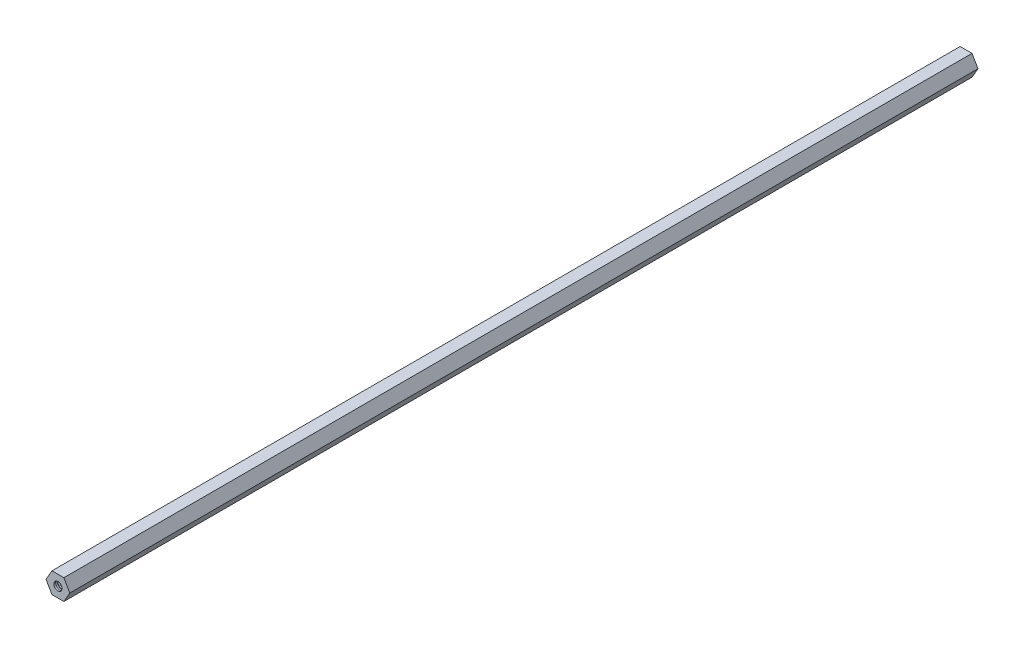
SolidWorks part; units mm, degrees
material "7075-T6 (SN)"
ref_plane "Alzado" through (0, 0, 0) normal (0, 0, 1) x (1, 0, 0)
ref_plane "Planta" through (0, 0, 0) normal (0, 1, 0) x (1, 0, 0)
ref_plane "Vista lateral" through (0, 0, 0) normal (1, 0, 0) x (0, 0, -1)
sketch "Croquis2" plane through (0, 0, 0) normal (0, 0, 1) x (1, 0, 0)
  line L1 (3.6662, -6.35) -> (7.3323, 0)
  line L2 (7.3323, 0) -> (3.6662, 6.35)
  line L3 (3.6662, 6.35) -> (-3.6662, 6.35)
  line L4 (-3.6662, 6.35) -> (-7.3323, 0)
  line L5 (-7.3323, 0) -> (-3.6662, -6.35)
  line L6 (-3.6662, -6.35) -> (3.6662, -6.35)
  circle A0 centre (0, 0) radius 6.35 construction
  dimension "D1" = 12.7
extrude "Extrusión Hex Profile" add sketch "Croquis2" along normal mid plane 558.8
sketch "Croquis3" plane through (0, 0, 0) normal (0, 0, 1) x (1, 0, 0)
  circle A0 centre (0, 0) radius 2.5527
  dimension "D1" = 5.1054
extrude "Tap Hole 1" cut sketch "Croquis3" against normal blind 19.05 from surface starting at face at (0, 0, 279.4)
extrude "Tap Hole 2" cut sketch "Croquis3<3>" along normal blind 19.05 from surface starting at face at (0, 0, -279.4)
sketch "Croquis3<3>" plane through (0, 0, 0) normal (0, 0, 1) x (1, 0, 0) same geometry as "Croquis3"
sketch "Croquis7" plane through (0, 0, 0) normal (0, 0, 1) x (1, 0, 0)
  circle A0 centre (0, 0) radius 6.8707
  dimension "D1" = 13.7414
extrude "ThunderHex" [suppressed] cut sketch "Croquis7" against normal through all both and the other way through all flip side to cut
sketch "Croquis8" plane through (0, 0, 0) normal (0, 1, 0) x (1, 0, 0)
  line L0 (0, -279.4) -> (-5.5563, -279.4) construction
  line L1 (3.6662, -279.4) -> (-3.6662, -279.4) construction
  line L3 (0, -279.4) -> (0, 0) construction
  line L4 (-5.5563, -279.4) -> (-6.35, -278.6062)
  line L5 (-6.35, -278.6062) -> (-6.35, -277.8125)
  line L6 (-6.35, -277.8125) -> (-5.9055, -277.8125)
  line L7 (-5.9055, -277.8125) -> (-5.9055, -276.225)
  line L8 (-5.9055, -276.225) -> (-12.7, -276.225)
  line L9 (-12.7, -276.225) -> (-12.7, -279.4)
  line L10 (-12.7, -279.4) -> (-5.5563, -279.4)
  line L11 (-3.6662, -279.4) -> (-7.3323, -279.4) construction
  dimension "D1" = 11.811
  dimension "D2" = 12.7
  dimension "D3" = 45
  dimension "D4" = 0.7937
  dimension "D6" = 0.7937
  dimension "D7" = 3.175
  dimension "D8" = 25.4
revolve "Retaining Ring 1" [suppressed] cut sketch "Croquis8" angle 360 about L3
sketch "Croquis9" plane through (0, 0, 0) normal (0, -1, 0) x (1, 0, 0)
  line L0 (0, -279.4) -> (-5.5563, -279.4) construction
  line L3 (0, -279.4) -> (0, 0) construction
  line L4 (-5.5563, -279.4) -> (-6.35, -278.6062)
  line L5 (-6.35, -278.6062) -> (-6.35, -277.8125)
  line L6 (-6.35, -277.8125) -> (-5.9055, -277.8125)
  line L7 (-5.9055, -277.8125) -> (-5.9055, -276.225)
  line L8 (-5.9055, -276.225) -> (-12.7, -276.225)
  line L9 (-12.7, -276.225) -> (-12.7, -279.4)
  line L10 (-12.7, -279.4) -> (-5.5563, -279.4)
  line L12 (-3.6662, -279.4) -> (3.6662, -279.4) construction
  line L13 (-7.3323, -279.4) -> (-3.6662, -279.4) construction
  dimension "D1" = 11.811
  dimension "D2" = 12.7
  dimension "D3" = 45
  dimension "D4" = 0.7937
  dimension "D6" = 0.7937
  dimension "D7" = 3.175
  dimension "D8" = 25.4
revolve "Retaining Ring 2" [suppressed] cut sketch "Croquis9" angle 360 about L3
sketch "Croquis10" plane through (0, 0, 0) normal (0, 1, 0) x (1, 0, 0)
  line L0 (0, -279.4) -> (0, 0) construction
  line L1 (3.6662, -279.4) -> (-3.6662, -279.4) construction
  line L2 (0, -279.4) -> (-5.5563, -279.4) construction
  line L3 (-3.6662, -279.4) -> (-7.3323, -279.4) construction
  line L4 (-5.5563, -279.4) -> (-6.35, -278.6062)
  line L5 (-6.35, -278.6062) -> (-6.35, -271.4498)
  line L6 (-6.35, -271.4498) -> (-9.525, -271.4498)
  line L7 (-9.525, -271.4498) -> (-9.525, -279.4)
  line L8 (-9.525, -279.4) -> (-5.5563, -279.4)
  dimension "D2" = 12.7
  dimension "D1" = 45
  dimension "D3" = 0.7937
  dimension "D4" = 7.9502
  dimension "D5" = 19.05
revolve "Round End 1" [suppressed] cut sketch "Croquis10" angle 360 about L0
sketch "Croquis12" plane through (0, 0, 0) normal (0, -1, 0) x (1, 0, 0)
  line L0 (0, -279.4) -> (0, 0) construction
  line L2 (0, -279.4) -> (-5.5563, -279.4) construction
  line L4 (-5.5563, -279.4) -> (-6.35, -278.6062)
  line L5 (-6.35, -278.6062) -> (-6.35, -271.4498)
  line L6 (-6.35, -271.4498) -> (-9.525, -271.4498)
  line L7 (-9.525, -271.4498) -> (-9.525, -279.4)
  line L8 (-9.525, -279.4) -> (-5.5563, -279.4)
  line L9 (-3.6662, -279.4) -> (3.6662, -279.4) construction
  dimension "D1" = 45
  dimension "D3" = 0.7937
  dimension "D4" = 7.9502
  dimension "D2" = 12.7
  dimension "D5" = 19.05
revolve "Round End 2" [suppressed] cut sketch "Croquis12" angle 360 about L0
thread "Rosca1" pitch 1.27 method cut profile "Perfil de rosca1" start angle 0, offset 0, length 0, pitch 1.27, diameter 5.1054
ref_plane "Plano1" through (2.5527, 0, -279.4) normal (0, -1, 0) x (1, 0, 0)
sketch "Perfil de rosca1" plane through (2.5527, 0, -279.4) normal (0, -1, 0) x (1, 0, 0)
  line L0 (0, 0) -> (0, 1.27) construction
  line L1 (0, 0) -> (0.6874, 0.3969)
  line L2 (0.6874, 0.3969) -> (0.6874, 0.5556)
  line L3 (0.6874, 0.5556) -> (0, 0.9525)
  line L4 (0.6874, 0.4762) -> (0, 0.4762) construction
  line L11 (0, 0) -> (0, 0.9525)
  point P2 (0, 0)
  dimension "Pitch" = 1.27
  dimension "Profile_Angle" = 60
  dimension "Profile_Land" = 0.1588
  dimension "Profile_Height" = 0.6874
thread "Rosca2" pitch 1.27 method cut profile "Perfil de rosca2" start angle 0, offset 0, length 0, pitch 1.27, diameter 5.1054
ref_plane "Plano2" through (-2.5527, 0, 279.4) normal (0, -1, 0) x (-1, 0, 0)
sketch "Perfil de rosca2" plane through (-2.5527, 0, 279.4) normal (0, -1, 0) x (-1, 0, 0)
  line L0 (0, 0) -> (0, 1.27) construction
  line L1 (0, 0) -> (0.6874, 0.3969)
  line L2 (0.6874, 0.3969) -> (0.6874, 0.5556)
  line L3 (0.6874, 0.5556) -> (0, 0.9525)
  line L4 (0.6874, 0.4762) -> (0, 0.4762) construction
  line L11 (0, 0) -> (0, 0.9525)
  point P2 (0, 0)
  dimension "Pitch" = 1.27
  dimension "Profile_Angle" = 60
  dimension "Profile_Land" = 0.1588
  dimension "Profile_Height" = 0.6874
equation "\"HexOD\"= 0.5pulgadas"
equation "\"Largo\"= 22pulgadas"
equation "\"D1@Croquis2\"=\"HexOD\""
equation "\"D1@Extrusión Hex Profile\" = \"Largo\""
equation "\"TapHole\"= IIF ( \"HexOD\" = 0.5pulgadas , 0.2010pulgadas , 0.190pulgadas )"
equation "\"D1@Croquis3\"=\"TapHole\""
equation "\"ProTapHole\"= 0.75pulgadas"
equation "\"D1@Tap Hole 1\" = \"ProTapHole\""
equation "\"D1@Tap Hole 2\" = \"ProTapHole\""
equation "\"ThunderHex\"= IIF ( \"HexOD\" = 0.5pulgadas , 0.541pulgadas , 0.4035pulgadas )"
equation "\"D1@Croquis7\"=\"ThunderHex\""
equation "\"D2@Croquis8\"=\"HexOD\""
equation "\"D1@Croquis8\"=if(\"HexOD\"=0.5pulgadas, 0.465pulgadas, 0.35pulgadas )"
equation "\"D2@Croquis9\"=\"HexOD\""
equation "\"D1@Croquis9\"=if(\"HexOD\"=0.5pulgadas, 0.465pulgadas, 0.35pulgadas )"
equation "\"D8@Croquis8\"=\"HexOD\"*2"
equation "\"D8@Croquis9\"=\"HexOD\"*2"
equation "\"D5@Croquis10\"=\"HexOD\"*1.5"
equation "\"D5@Croquis12\"=\"HexOD\"*1.5"
equation "\"D4@Croquis10\"=if( \"D2@Croquis10\"=<0.375, 0.28, 0.313)"
equation "\"D4@Croquis12\"=if( \"D2@Croquis10\"=<0.375, 0.28, 0.313)"
